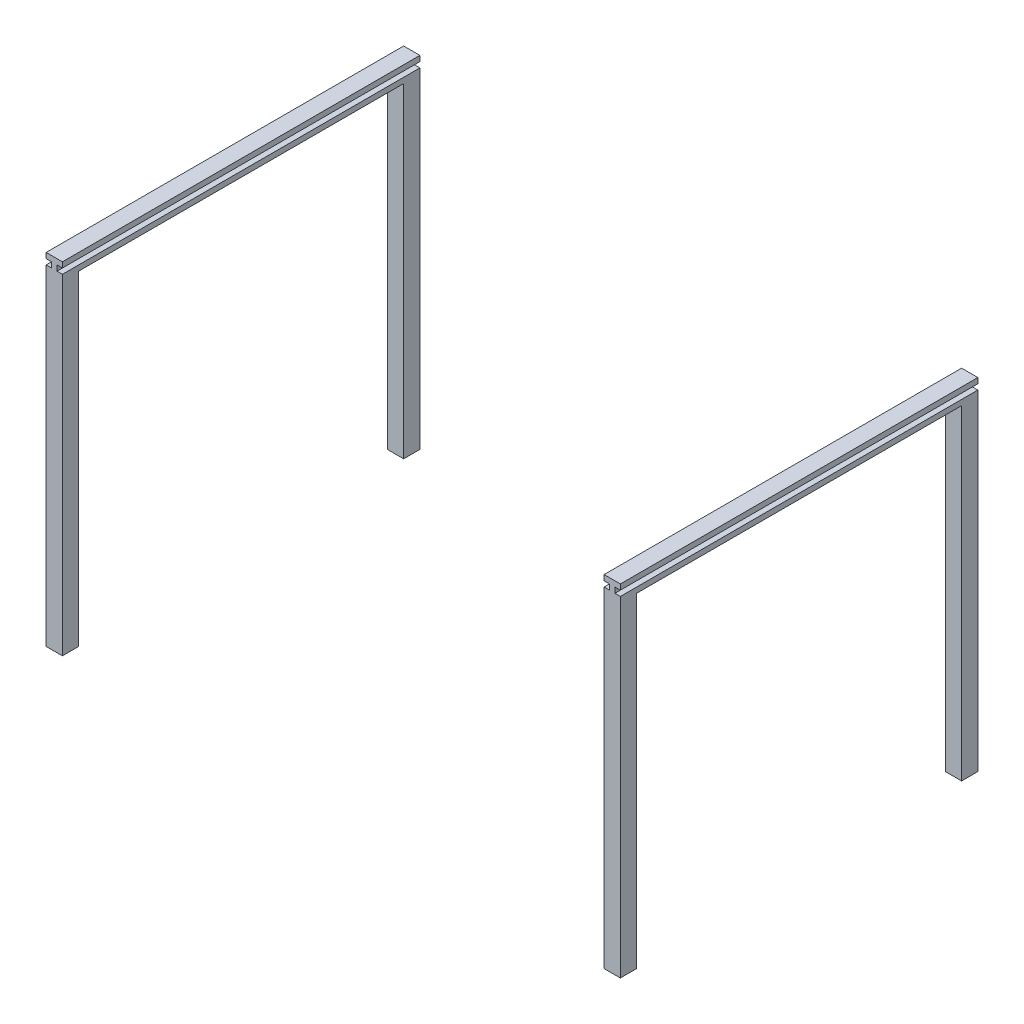
SolidWorks part; units mm, degrees
ref_plane "Front Plane" through (0, 0, 0) normal (0, 0, 1) x (1, 0, 0)
ref_plane "Top Plane" through (0, 0, 0) normal (0, 1, 0) x (1, 0, 0)
ref_plane "Right Plane" through (0, 0, 0) normal (1, 0, 0) x (0, 0, -1)
other "Center of Mass"
sketch "Sketch1" plane through (0, 0, 0) normal (0, 1, 0) x (1, 0, 0)
  line L0 (-55, 0) -> (55, 0) construction
  line L1 (-2650, 1650) -> (-2500, 1650)
  line L2 (-2650, 1650) -> (-2650, 1500)
  line L3 (-2650, 1500) -> (-2500, 1500)
  line L4 (-2500, 1650) -> (-2500, 1500)
  line L5 (-2650, 1650) -> (-2500, 1500) construction
  line L6 (-2650, 1500) -> (-2500, 1650) construction
  line L7 (-2650, -1500) -> (-2500, -1650) construction
  line L8 (-2650, -1650) -> (-2500, -1500) construction
  line L9 (-2500, -1650) -> (-2500, -1500)
  line L10 (-2650, -1500) -> (-2500, -1500)
  line L11 (-2650, -1650) -> (-2650, -1500)
  line L12 (-2650, -1650) -> (-2500, -1650)
  line L13 (0, -55) -> (0, 55) construction
  line L14 (2650, 1500) -> (2500, 1650) construction
  line L15 (2650, 1650) -> (2500, 1500) construction
  line L16 (2500, 1650) -> (2500, 1500)
  line L17 (2650, 1500) -> (2500, 1500)
  line L18 (2650, 1650) -> (2650, 1500)
  line L19 (2650, 1650) -> (2500, 1650)
  line L20 (2650, -1650) -> (2500, -1500) construction
  line L21 (2650, -1500) -> (2500, -1650) construction
  line L22 (2650, -1650) -> (2500, -1650)
  line L23 (2650, -1650) -> (2650, -1500)
  line L24 (2650, -1500) -> (2500, -1500)
  line L25 (2500, -1650) -> (2500, -1500)
  point P0 (-2575, 1575)
  point P14 (-2575, -1575)
  point P21 (2575, 1575)
  point P26 (2575, -1575)
  dimension "D1" = 150
  dimension "D2" = 2500
  dimension "1" = 150
  dimension "D3" = 1500
extrude "Boss-Extrude1" add sketch "Sketch1" along normal blind 3000
ref_plane "Plane1" through (0, 0, 1650) normal (0, 0, 1) x (1, 0, 0)
sketch "Sketch2" plane through (0, 0, 1650) normal (0, 0, 1) x (1, 0, 0)
  line L21 (-2500, 3000) -> (-2650, 3000)
  line L22 (-2650, 3000) -> (-2650, 3050)
  line L23 (-2650, 3050) -> (-2600, 3050)
  line L24 (-2600, 3050) -> (-2600, 3100)
  line L27 (-2600, 3100) -> (-2650, 3100)
  line L28 (-2650, 3100) -> (-2650, 3150)
  line L29 (-2500, 3000) -> (-2500, 3050)
  line L30 (-2500, 3050) -> (-2550, 3050)
  line L31 (-2550, 3050) -> (-2550, 3100)
  line L32 (-2550, 3100) -> (-2500, 3100)
  line L33 (-2500, 3100) -> (-2500, 3150)
  line L34 (-2500, 3150) -> (-2650, 3150)
  line L35 (0, -1732.5) -> (0, 1732.5) construction
  line L36 (2500, 3150) -> (2650, 3150)
  line L37 (2500, 3100) -> (2500, 3150)
  line L38 (2550, 3100) -> (2500, 3100)
  line L39 (2550, 3050) -> (2550, 3100)
  line L40 (2500, 3050) -> (2550, 3050)
  line L41 (2500, 3000) -> (2500, 3050)
  line L42 (2650, 3100) -> (2650, 3150)
  line L43 (2600, 3100) -> (2650, 3100)
  line L44 (2600, 3050) -> (2600, 3100)
  line L45 (2650, 3050) -> (2600, 3050)
  line L46 (2650, 3000) -> (2650, 3050)
  line L47 (2500, 3000) -> (2650, 3000)
  point P12 (-2650, 3025)
  dimension "D1" = 150
  dimension "D2" = 50
  dimension "D3" = 50
  dimension "D4" = 150
  dimension "D5" = 50
  dimension "D6" = 50
  dimension "D7" = 50
  dimension "D8" = 50
extrude "Boss-Extrude2" add sketch "Sketch2" against normal blind 3300
ref_axis "Base_Axis" through (0, 3307.5, 0) along (0, -1, 0)
